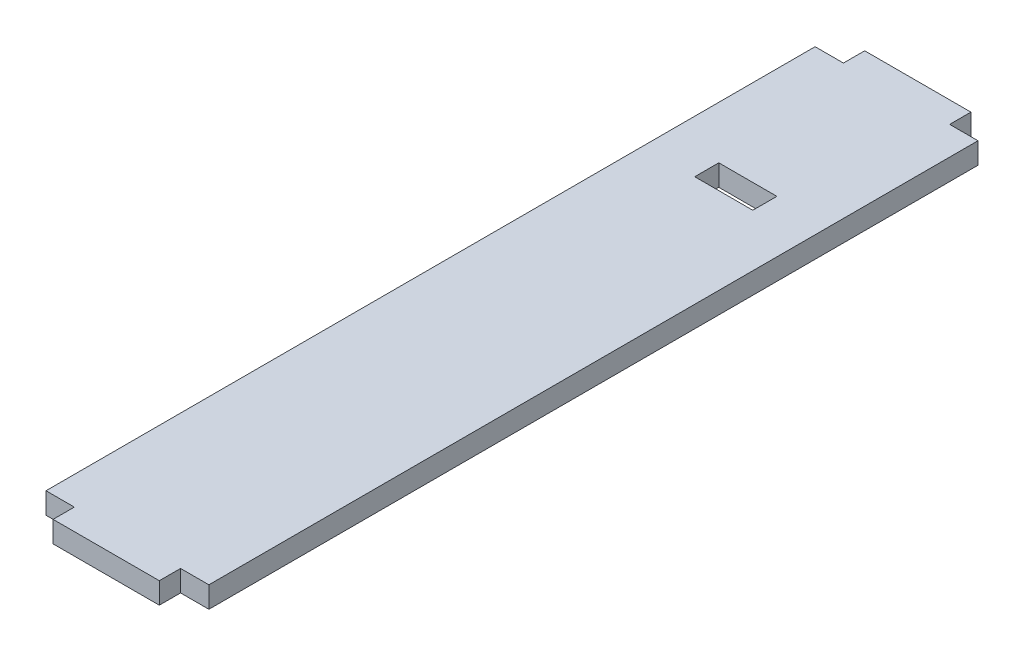
SolidWorks part; units mm, degrees
material "AISI 304"
ref_plane "Front Plane" through (0, 0, 0) normal (0, 0, 1) x (1, 0, 0)
ref_plane "Top Plane" through (0, 0, 0) normal (0, 1, 0) x (1, 0, 0)
ref_plane "Right Plane" through (0, 0, 0) normal (1, 0, 0) x (0, 0, -1)
sketch "Sketch1" plane through (0, 0, 0) normal (0, 1, 0) x (1, 0, 0)
  line L0 (3.75, 27.15) -> (5.75, 27.15)
  line L1 (-5.75, -27.15) -> (-3.75, -27.15)
  line L2 (-5.75, -27.15) -> (-5.75, -16.6)
  line L3 (-5.75, 27.15) -> (-3.75, 27.15)
  line L4 (5.75, -27.15) -> (5.75, -14.1)
  line L5 (-5.75, -27.15) -> (5.75, 27.15) construction
  line L6 (-5.75, 27.15) -> (5.75, -27.15) construction
  line L8 (3.75, 27.15) -> (3.75, 28.65)
  line L9 (3.75, 28.65) -> (-3.75, 28.65)
  line L10 (-3.75, 27.15) -> (-3.75, 28.65)
  line L12 (-3.75, -27.15) -> (-3.75, -28.65)
  line L13 (-3.75, -28.65) -> (3.75, -28.65)
  line L14 (3.75, -27.15) -> (3.75, -28.65)
  line L15 (3.75, -27.15) -> (5.75, -27.15)
  line L16 (-5.75, -14.9) -> (-5.75, 27.15)
  line L21 (5.75, -12.4) -> (5.75, 27.15)
  line L26 (0, 0) -> (0, 53.4412) construction
  line L31 (-5.75, -16.6) -> (-5.75, -14.9)
  line L32 (-2.05, 14.95) -> (2.05, 14.95)
  line L33 (-2.05, 14.95) -> (-2.05, 16.65)
  line L34 (-2.05, 16.65) -> (2.05, 16.65)
  line L35 (2.05, 14.95) -> (2.05, 16.65)
  line L36 (-2.05, 14.95) -> (2.05, 16.65) construction
  line L37 (-2.05, 16.65) -> (2.05, 14.95) construction
  line L38 (5.75, -12.4) -> (5.75, -14.1)
  point P0 (0, 0)
  point P23 (0, 15.8)
  dimension "D1" = 7.5
  dimension "D2" = 2
  dimension "D3" = 2
  dimension "D4" = 1.5
  dimension "D5" = 2
  dimension "D6" = 2
  dimension "D7" = 1.5
  dimension "D8" = 54.3
  dimension "D11" = 1.7
  dimension "D12" = 3.7
  dimension "D13" = 12
extrude "Boss-Extrude1" add sketch "Sketch1" along normal blind 1.5
